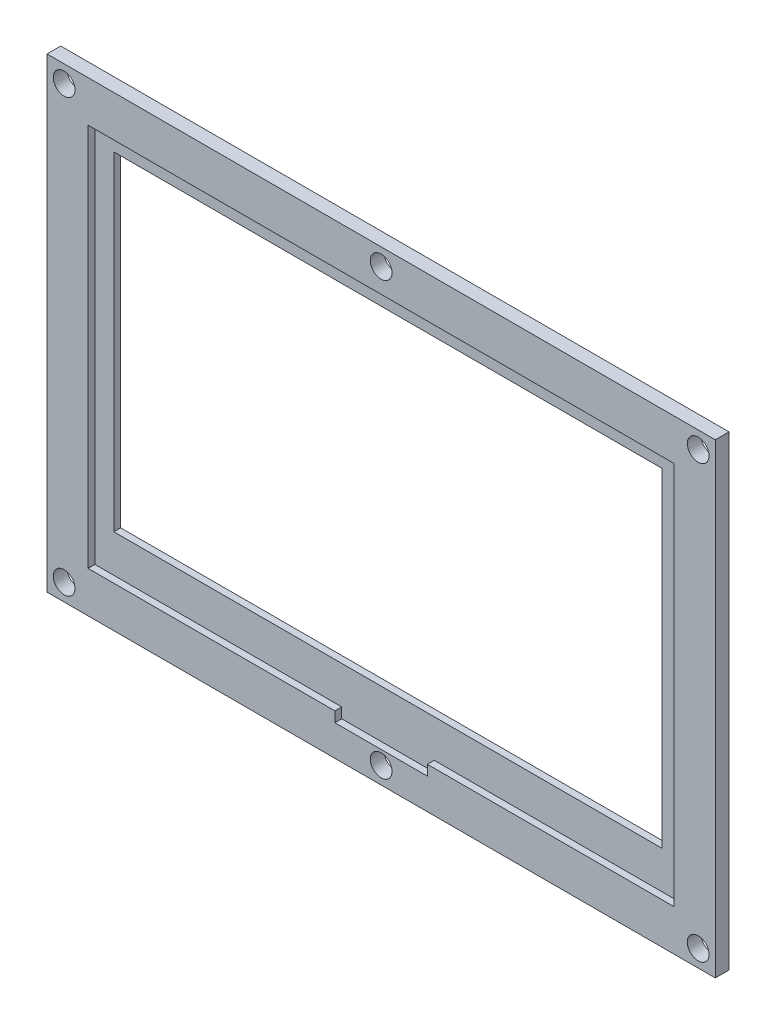
SolidWorks part; units mm, degrees
ref_plane "Front Plane" through (0, 0, 0) normal (0, 0, 1) x (1, 0, 0)
ref_plane "Top Plane" through (0, 0, 0) normal (0, 1, 0) x (1, 0, 0)
ref_plane "Right Plane" through (0, 0, 0) normal (1, 0, 0) x (0, 0, -1)
sketch "Sketch1" plane through (0, 0, 0) normal (0, 0, 1) x (1, 0, 0)
  line L1 (85.5, -56) -> (-85.5, -56)
  line L2 (85.5, -56) -> (85.5, 56)
  line L3 (85.5, 56) -> (-85.5, 56)
  line L4 (-85.5, -56) -> (-85.5, 56)
  line L5 (85.5, -56) -> (-85.5, 56) construction
  line L6 (85.5, 56) -> (-85.5, -56) construction
  line L11 (80, -45) -> (-80, -45)
  line L12 (80, -45) -> (80, 51)
  line L13 (80, 51) -> (-80, 51)
  line L14 (-80, -45) -> (-80, 51)
  line L15 (80, -45) -> (-80, 51) construction
  line L16 (80, 51) -> (-80, -45) construction
  line L17 (-13.5, -56) -> (13.5, -56)
  line L18 (-13.5, -56) -> (-13.5, -59)
  line L19 (-13.5, -59) -> (13.5, -59)
  line L20 (13.5, -56) -> (13.5, -59)
  line L21 (97.5, 68) -> (-97.5, 68)
  line L22 (97.5, 68) -> (97.5, -68)
  line L23 (97.5, -68) -> (-97.5, -68)
  line L24 (-97.5, 68) -> (-97.5, -68)
  line L25 (97.5, 68) -> (-97.5, -68) construction
  line L26 (97.5, -68) -> (-97.5, 68) construction
  point P0 (0, 0)
  point P6 (0, 0)
  point P7 (0, 3)
  point P16 (0, 0)
  dimension "D1" = 171
  dimension "D2" = 112
  dimension "D3" = 96
  dimension "D4" = 160
  dimension "D5" = 5
  dimension "D6" = 72
  dimension "D7" = 27
  dimension "D8" = 3
  dimension "D9" = 12
  dimension "D10" = 17.5
  dimension "D11" = 12
extrude "Boss-Extrude1" add sketch "Sketch1" against normal blind 2 contours L4 L1 L2 L3 L11 L14 L13 L12 | L21 L24 L23 L22 L1 L20 L19 L18 L4 L3 L2 | L20 L1 L18 L19 region at (49.5, -53.9559, 0) region at (0, -57.5, 0) region at (95.1226, 0, 0)
extrude "Boss-Extrude2" add sketch "Sketch1<3>" along normal blind 2 contours L21 L24 L23 L22 L1 L20 L19 L18 L4 L3 L2 region at (95.1226, 0, 0)
sketch "Sketch1<3>" plane through (0, 0, 0) normal (0, 0, 1) x (1, 0, 0) same geometry as "Sketch1"
sketch "Sketch2" plane through (0, 0, 2) normal (0, 0, 1) x (1, 0, 0)
  line L0 (97.5, 68) -> (-97.5, 68) construction
  line L1 (92.5, -63) -> (-92.5, -63) construction
  line L2 (92.5, -63) -> (92.5, 63) construction
  line L3 (92.5, 63) -> (-92.5, 63) construction
  line L4 (-92.5, -63) -> (-92.5, 63) construction
  line L5 (92.5, -63) -> (-92.5, 63) construction
  line L6 (92.5, 63) -> (-92.5, -63) construction
  line L7 (-97.5, 68) -> (-97.5, -68) construction
  circle A0 centre (-92.5, 63) radius 3.175
  circle A1 centre (0, 63) radius 3.175
  circle A2 centre (92.5, 63) radius 3.175
  circle A3 centre (92.5, -63) radius 3.175
  circle A4 centre (0, -63) radius 3.175
  circle A5 centre (-92.5, -63) radius 3.175
  point P0 (0, 0)
  dimension "D1" = 6.35
  dimension "D2" = 5
  dimension "D3" = 5
extrude "Cut-Extrude1" cut sketch "Sketch2" against normal through all
